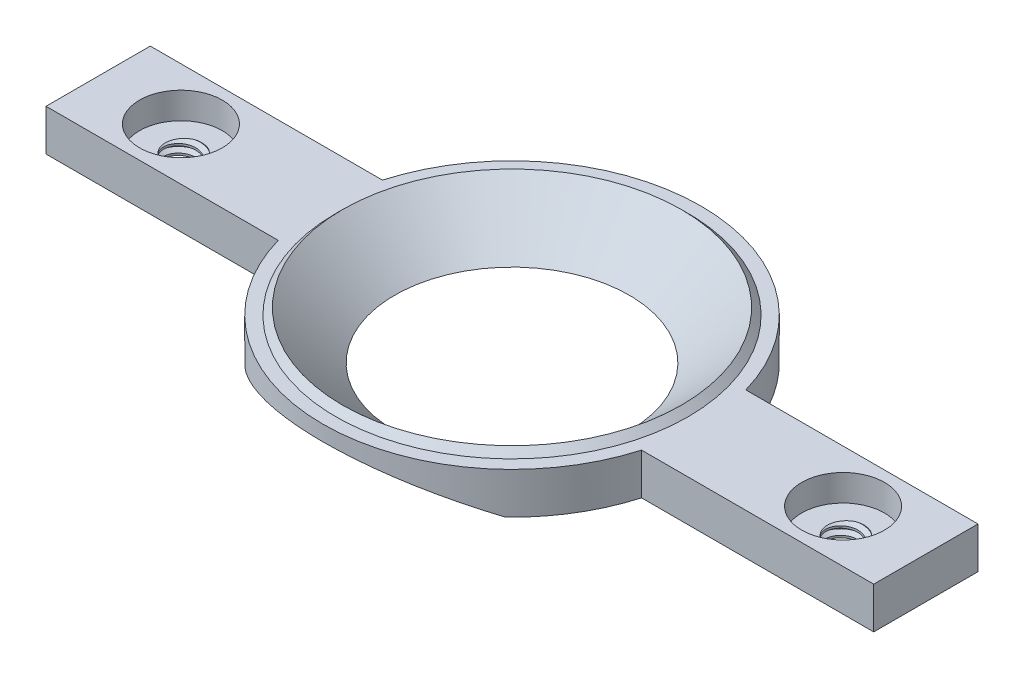
SolidWorks part; units mm, degrees
material "AISI Type 316L stainless steel"
ref_plane "Front Plane" through (0, 0, 0) normal (0, 0, 1) x (1, 0, 0)
ref_plane "Top Plane" through (0, 0, 0) normal (0, 1, 0) x (1, 0, 0)
ref_plane "Right Plane" through (0, 0, 0) normal (1, 0, 0) x (0, 0, -1)
sketch "Sketch1" plane through (0, 0, 0) normal (0, 1, 0) x (1, 0, 0)
  line L0 (0, -1000) -> (0, 49000) construction
  line L1 (-15.875, -2) -> (15.875, -2)
  line L2 (-15.875, -2) -> (-15.875, 2)
  line L3 (-15.875, 2) -> (15.875, 2)
  line L4 (15.875, -2) -> (15.875, 2)
  circle A0 centre (0, 0) radius 7.25
  circle A1 centre (0, 0) radius 6.75
  circle A2 centre (-12.7, 0) radius 0.7937
  circle A4 centre (12.7, 0) radius 0.7937
  point P4 (0, 2)
  point P6 (-15.875, 0)
  dimension "D3" = 14.5
  dimension "D4" = 0.5
  dimension "D5" = 1.5875
  dimension "D6" = 12.7
  dimension "D1" = 31.75
  dimension "D2" = 4
extrude "Boss-Extrude1" add sketch "Sketch1" along normal mid plane 1.5875 contours A0 L3 L2 L1 A2 | A1 L3 A0 L1 | A0 L0 A1 L1 | A1 L0 A0 L3 | L0 A0 L1 A1 | L0 A1 L3 A0 | A0 L1 L4 L3 A4 | A1 L1 A0 L3 region at (-4.31, 0, 5.7209) region at (0.0872, 0, 7) region at (-6.9023, 0, 0) region at (-11.4443, 0, 0) region at (11.4443, 0, 0) region at (6.9023, 0, 0) region at (-4.31, 0, -5.7209) region at (4.31, 0, -5.7209)
sketch "Sketch5" plane through (0, 0, 0) normal (0, 0, 1) x (1, 0, 0)
  line L0 (0, -1000) -> (0, 49000) construction
  line L1 (-6.7568, 0.7937) -> (-6.5, 1.0506)
  line L3 (-6.7568, 0.7937) -> (-6.7568, -0.7937)
  line L4 (-6.7568, -0.7937) -> (-5.0003, -0.7937)
  line L6 (-4.5, -0.7938) -> (-6.7568, -0.7937)
  line L7 (-6.7568, 0.7937) -> (-6.7568, -0.7937)
  line L8 (-4.5, -0.7938) -> (-5.0003, -0.7937)
  line L9 (-6.5, 1.0506) -> (-4.5, -0.7938)
  line L10 (-15.875, -0.7937) -> (-6.9687, -0.7937) construction
  line L11 (-6.7568, -0.7937) -> (-4.5, -0.7938)
  point P7 (-6.7568, 0)
  dimension "D2" = 4.5
  dimension "D3" = 135
  dimension "D4" = 6.5
  dimension "D5" = 0.3632
revolve "Revolve1" add sketch "Sketch5" angle 360 about L0 region at (-5.9861, -0.1318, 0)
sketch "Sketch6" plane through (0, 0, 0) normal (1, 0, 0) x (0, 0, -1)
  line L1 (5.25, -0.7937) -> (7.25, 0.2063)
  line L3 (0, -1000) -> (0, 49000) construction
  line L5 (0, -1000) -> (0, 49000) construction
  line L6 (-7.25, 0.2063) -> (-7.25, -0.7937)
  line L7 (-7.25, -0.7937) -> (-5.25, -0.7937)
  line L8 (-5.25, -0.7937) -> (-7.25, 0.2063)
  line L9 (7.25, -0.7937) -> (5.25, -0.7937)
  line L10 (-7.25, -0.7937) -> (-2, -0.7937) construction
  line L11 (7.25, 0.2063) -> (7.25, -0.7937)
  line L12 (-2, 0.7937) -> (-7.25, 0.7937) construction
  line L13 (-2, -0.7937) -> (2, -0.7937)
  line L14 (-2, -0.7937) -> (-2, -1.7937)
  line L15 (-2, -1.7937) -> (2, -1.7937)
  line L16 (2, -0.7937) -> (2, -1.7937)
  dimension "D1" = 1
  dimension "D2" = 2
  dimension "D3" = 1
extrude "Cut-Extrude1" cut sketch "Sketch6" along normal up to surface (15.875 mm away) from surface up to face at (15.875, 0, 0) starting at face at (-15.875, 0, 0)
thread "Thread1" pitch 0.3175 method extrude profile "Thread Profile2" start angle 0, offset 0, length 0, pitch 0.3175, diameter 1.5875
ref_plane "Plane2" through (-13.4937, 0.7937, 0) normal (0, 0, 1) x (-1, 0, 0)
sketch "Thread Profile2" plane through (-13.4937, 0.7937, 0) normal (0, 0, 1) x (-1, 0, 0)
  line L0 (0, 0) -> (0, 0.3175) construction
  line L11 (0, 0) -> (0, 0.2778)
  line L12 (0, 0.2778) -> (-0.1719, 0.1786)
  line L13 (-0.1719, 0.1786) -> (-0.1719, 0.0992)
  line L15 (-0.1719, 0.0992) -> (0, 0)
  line L17 (-0.1719, 0.1389) -> (0, 0.1389) construction
  point P2 (0, 0)
  dimension "Pitch" = 0.3175
  dimension "Profile_Angle" = 60
  dimension "Profile_Land" = 0.0794
  dimension "Profile_Height" = 0.1719
thread "Thread2" pitch 0.3175 method extrude profile "Thread Profile3" start angle 0, offset 0, length 0, pitch 0.3175, diameter 1.5875
ref_plane "Plane3" through (11.9062, 0.7937, 0) normal (0, 0, 1) x (-1, 0, 0)
sketch "Thread Profile3" plane through (11.9062, 0.7937, 0) normal (0, 0, 1) x (-1, 0, 0)
  line L0 (0, 0) -> (0, 0.3175) construction
  line L11 (0, 0) -> (0, 0.2778)
  line L12 (0, 0.2778) -> (-0.1719, 0.1786)
  line L13 (-0.1719, 0.1786) -> (-0.1719, 0.0992)
  line L15 (-0.1719, 0.0992) -> (0, 0)
  line L17 (-0.1719, 0.1389) -> (0, 0.1389) construction
  point P2 (0, 0)
  dimension "Pitch" = 0.3175
  dimension "Profile_Angle" = 60
  dimension "Profile_Land" = 0.0794
  dimension "Profile_Height" = 0.1719
sketch "Sketch14" plane through (0, 0.7937, 0) normal (0, 1, 0) x (1, 0, 0)
  line L0 (0, -1.1672) -> (0, 1.1672) construction
  circle A0 centre (12.7, 0) radius 1.5875
  circle A1 centre (-12.7, 0) radius 1.5875
  dimension "D1" = 3.175
extrude "Cut-Extrude2" cut sketch "Sketch14" against normal blind 1.016 contours A1 | A0 body kept at (-6.9687, 0.7937, 2)
